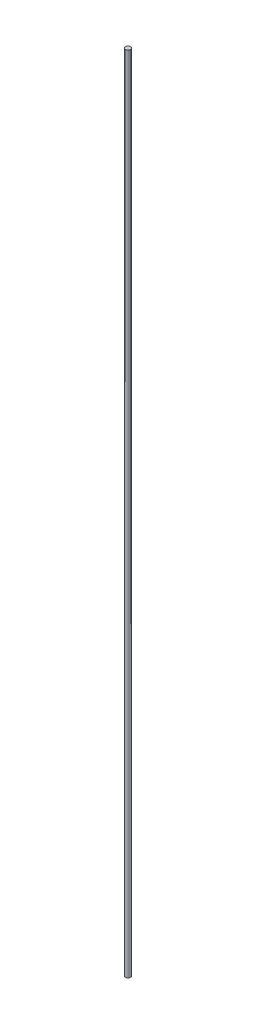
SolidWorks part; units mm, degrees
ref_plane "Спереди" through (0, 0, 0) normal (0, 0, 1) x (1, 0, 0)
ref_plane "Сверху" through (0, 0, 0) normal (0, 1, 0) x (1, 0, 0)
ref_plane "Справа" through (0, 0, 0) normal (1, 0, 0) x (0, 0, -1)
sketch "Эскиз2" plane through (0, 0, 0) normal (0, 0, 1) x (1, 0, 0)
  line L0 (0, 326.1485) -> (-5, 326.1485) construction
  line L5 (-2.5, 326.1485) -> (0, 326.1485)
  line L6 (-2.5, 326.1485) -> (-2.5, -477.2515)
  line L7 (-2.5, -477.2515) -> (0, -477.2515)
  line L8 (0, 326.1485) -> (0, -477.2515)
  line L9 (-2.5, 326.1485) -> (0, -477.2515) construction
  line L10 (-2.5, -477.2515) -> (0, 326.1485) construction
  line L13 (-506.5, -477.2515) -> (23.5, -477.2515) construction
  point P0 (-1.25, -75.5515)
  point P12 (0, 0)
  dimension "D1" = 2.5
revolve "Повернуть1" add sketch "Эскиз2" angle 360 about L6
equation "\"Ширина груза\"= 420"
equation "\"Глубина груза\"= 490"
equation "\"Высота груза\"= 297"
equation "\"Ширина ячейки\"= \"Ширина груза\" + 10"
equation "\"Глубина ячейки\"= \"Глубина груза\" + 10"
equation "\"Высота ячейки\"= \"Высота груза\" + 10 + 13"
equation "\"Колво ячеек ширина\"= 2"
equation "\"Колво ячеек высота\"= 2"
equation "\"Толщина стенки\" = 6"
equation "\"Крепление дверцы\"= 5 "
equation "\"Ширина рейки\"= \"Толщина шестерни\""
equation "\"Высота рейки\"= 20"
equation "\"Высота пола\"= \"Толщина стенки\" * 2"
equation "\"Колво полозьев\"= 5"
equation "\"Отступ рейки\"= 20"
equation "\"Глубина каретки\"= \"Глубина ячейки\" + 30 + \"Мотор Y высота корпуса\" + 20"
equation "\"Длинна рейки\" = (\"Ширина ячейки\" + \"Толщина стенки\" + \"Крепление дверцы\") * \"Колво ячеек ширина\" + \"Ширина ячейки выгрузки\" * \"Колво выгрузки\" + \"Толщина стенки\" + \"Отступ крепления мотора фиксации\" * 2 - \"Крепление дверцы\" * \"Колво ячеек ширина\""
equation "\"Отступ шпильки\"= 26"
equation "\"Диаметр шпильки\"= 5"
equation "\"Длинна шпильки\"= ( \"Высота ячейки\" + \"Толщина стенки\" + \"Высота пола\" ) * \"Колво ячеек высота\" + ( \"Толщина стенки\" + \"Отступ рейки\" ) * 2 "
equation "\"D1@Эскиз2\"= \"Диаметр шпильки\" / 2"
equation "\"Ширина пластины\"= 50  "
equation "\"Высота зона выгрузки\"= \"Высота ячейки\" * 2 + \"Толщина стенки\" * 2"
equation "\"Колво выгрузки\"= 1"
equation "\"Отступ крепления мотора фиксации\" = (\"Ширина пластины\" + 20 - \"Толщина стенки\") / 2"
equation "\"Мотор X ширина корпуса\"= 42.3"
equation "\"Мотор X высота корпуса\"= 42.3"
equation "\"Мотор X длина корпуса\"= 40"
equation "\"Мотор X вылет вала\"= 19.8"
equation "\"Мотор Y ширина корпуса\"= 42.3"
equation "\"Мотор Y высота корпуса\"= 42.3"
equation "\"Мотор Y длина корпуса\"= 48"
equation "\"Мотор Y вылет вала\"= 30"
equation "\"Мотор Z ширина корпуса\"= 42"
equation "\"Мотор Z высота корпуса\"= 42"
equation "\"Мотор Z длина корпуса\"= 40"
equation "\"Мотор Z вылет вала\"= 23"
equation "\"Мотор диаметр вала ПРЕДВ\"= 5"
equation "\"Мотор шаг крепления ПРЕДВ\"= 31"
equation "\"Мотор диаметр отверстий ПРЕДВ\"= 3"
equation "\"Мотор глубина отверстий ПРЕДВ\"= 4.5"
equation "\"Мотор диаметр буртика ПРЕДВ\"= 22"
equation "\"Мотор высота буртика ПРЕДВ\"= 2"
equation "\"Мотор диаметр шкива ПРЕДВ\"= 16"
equation "\"Мотор длина шкива ПРЕДВ\"= 12"
equation "\"Мотор отступ шкива ПРЕДВ\"= 5"
equation "\"Мотор X шаг градусов\"= 1.8"
equation "\"Мотор X ток А\"= 1.5"
equation "\"Мотор X сопротивление Ом\"= 1.3"
equation "\"Мотор X индуктивность мГн\"= 2"
equation "\"Мотор Y шаг градусов\"= 1.8"
equation "\"Мотор Y ток А\"= 2.2"
equation "\"Мотор Y сопротивление Ом\"= 0.9"
equation "\"Мотор Y индуктивность мГн\"= 2"
equation "\"Мотор Z шаг градусов\"= 1.8"
equation "\"Мотор Z ток А\"= 1"
equation "\"Мотор Z сопротивление Ом\"= 4"
equation "\"Мотор Z индуктивность мГн\"= 8"
equation "\"Мотор Y диаметр ротора\"= 25.78"
equation "\"Ширина ячейки выгрузки\"= \"Ширина ячейки\" + \"Толщина стенки\" + \"Отступ крепления мотора фиксации\"*2"
